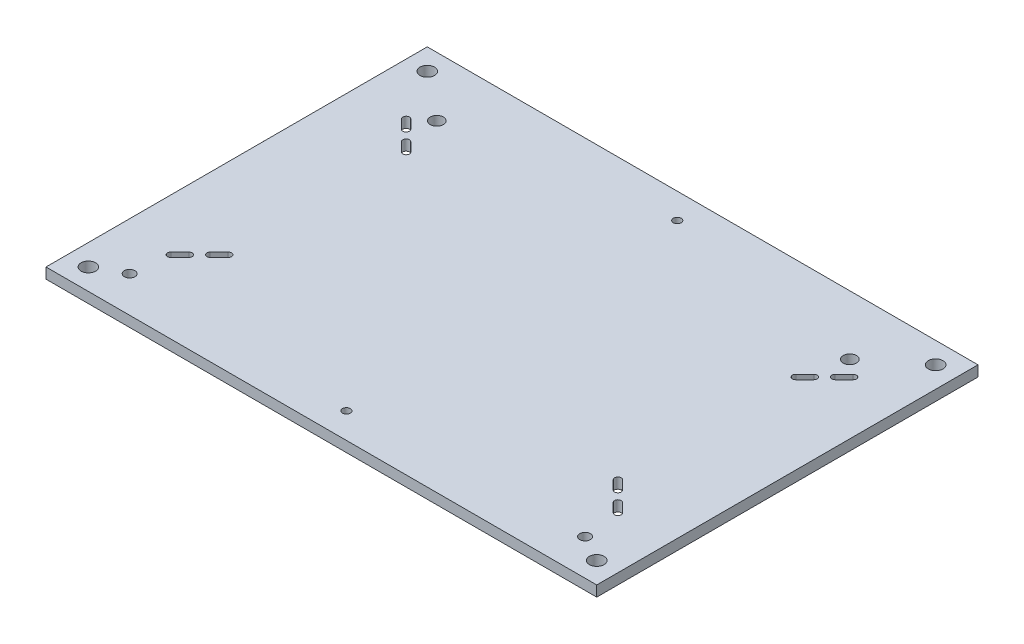
SolidWorks part; units mm, degrees
ref_plane "Front Plane" through (0, 0, 0) normal (0, 0, 1) x (1, 0, 0)
ref_plane "Top Plane" through (0, 0, 0) normal (0, 1, 0) x (1, 0, 0)
ref_plane "Right Plane" through (0, 0, 0) normal (1, 0, 0) x (0, 0, -1)
sketch "Sketch1" plane through (0, 0, 0) normal (0, 1, 0) x (1, 0, 0)
  line L1 (0, 0) -> (330.2, 0)
  line L2 (0, 0) -> (0, -228.6)
  line L3 (0, -228.6) -> (330.2, -228.6)
  line L4 (330.2, 0) -> (330.2, -228.6)
  dimension "D1" = 330.2
  dimension "D2" = 228.6
extrude "base plate" add sketch "Sketch1" against normal blind 6.35
sketch "center lines" plane through (0, 0, 0) normal (0, 1, 0) x (1, 0, 0)
  line L0 (165.1, 0) -> (165.1, -228.6) construction
  line L1 (330.2, 0) -> (0, 0) construction
  line L2 (0, -228.6) -> (330.2, -228.6) construction
  line L3 (0, -114.3) -> (330.2, -114.3) construction
  line L4 (0, 0) -> (0, -228.6) construction
  line L5 (330.2, -228.6) -> (330.2, 0) construction
sketch "Sketch3" plane through (0, 0, 0) normal (0, 1, 0) x (1, 0, 0)
  line L0 (21.0672, -185.8525) -> (30.0475, -194.8328)
  line L1 (30.0475, -194.8328) -> (60.5804, -164.2999)
  line L2 (60.5804, -164.2999) -> (51.6001, -155.3196)
  line L3 (51.6001, -155.3196) -> (21.0672, -185.8525)
  line L4 (31.0806, -184.8194) -> (36.4687, -179.4313) construction
  line L5 (29.6664, -183.4052) -> (35.0545, -178.0171)
  line L6 (32.4948, -186.2336) -> (37.8829, -180.8455)
  line L7 (0, -228.6) -> (330.2, -228.6) construction
  line L8 (48.2774, -167.6226) -> (42.8893, -173.0107) construction
  line L9 (49.6916, -169.0368) -> (44.3035, -174.425)
  line L10 (165.1, 0) -> (165.1, -228.6) construction
  line L11 (0, -114.3) -> (330.2, -114.3) construction
  line L12 (60.5804, -64.3001) -> (51.6001, -73.2804)
  line L13 (30.0475, -33.7672) -> (60.5804, -64.3001)
  line L14 (21.0672, -42.7475) -> (30.0475, -33.7672)
  line L15 (51.6001, -73.2804) -> (21.0672, -42.7475)
  line L16 (300.1525, -33.7672) -> (269.6196, -64.3001)
  line L17 (309.1328, -42.7475) -> (300.1525, -33.7672)
  line L18 (278.5999, -73.2804) -> (309.1328, -42.7475)
  line L19 (269.6196, -64.3001) -> (278.5999, -73.2804)
  line L20 (269.6196, -164.2999) -> (278.5999, -155.3196)
  line L21 (300.1525, -194.8328) -> (269.6196, -164.2999)
  line L22 (309.1328, -185.8525) -> (300.1525, -194.8328)
  line L23 (278.5999, -155.3196) -> (309.1328, -185.8525)
  line L24 (46.8632, -166.2084) -> (41.475, -171.5965)
  line L25 (31.0806, -43.7806) -> (36.4687, -49.1687) construction
  line L26 (29.6664, -45.1948) -> (35.0545, -50.5829)
  line L27 (32.4948, -42.3664) -> (37.8829, -47.7545)
  line L28 (48.2774, -60.9774) -> (42.8893, -55.5893) construction
  line L29 (49.6916, -59.5632) -> (44.3035, -54.175)
  line L30 (46.8632, -62.3916) -> (41.475, -57.0035)
  line L31 (299.1194, -43.7806) -> (293.7313, -49.1687) construction
  line L32 (300.5336, -45.1948) -> (295.1455, -50.5829)
  line L33 (297.7052, -42.3664) -> (292.3171, -47.7545)
  line L34 (281.9226, -60.9774) -> (287.3107, -55.5893) construction
  line L35 (280.5084, -59.5632) -> (285.8965, -54.175)
  line L36 (283.3368, -62.3916) -> (288.725, -57.0035)
  line L37 (281.9226, -167.6226) -> (287.3107, -173.0107) construction
  line L38 (280.5084, -169.0368) -> (285.8965, -174.425)
  line L39 (283.3368, -166.2084) -> (288.725, -171.5965)
  line L40 (299.1194, -184.8194) -> (293.7313, -179.4313) construction
  line L41 (300.5336, -183.4052) -> (295.1455, -178.0171)
  line L42 (297.7052, -186.2336) -> (292.3171, -180.8455)
  line L43 (51.6001, -164.2999) -> (51.6001, -155.3196)
  line L44 (60.5804, -164.2999) -> (51.6001, -164.2999)
  line L45 (51.6001, -64.3001) -> (51.6001, -73.2804)
  line L46 (60.5804, -64.3001) -> (51.6001, -64.3001)
  line L47 (278.5999, -64.3001) -> (278.5999, -73.2804)
  line L48 (269.6196, -64.3001) -> (278.5999, -64.3001)
  line L49 (278.5999, -164.2999) -> (278.5999, -155.3196)
  line L50 (269.6196, -164.2999) -> (278.5999, -164.2999)
  arc A0 (29.6664, -183.4052) -> (32.4948, -186.2336) centre (31.0806, -184.8194) ccw
  arc A1 (37.8829, -180.8455) -> (35.0545, -178.0171) centre (36.4687, -179.4313) ccw
  arc A2 (49.6916, -169.0368) -> (46.8632, -166.2084) centre (48.2774, -167.6226) ccw
  arc A3 (41.475, -171.5965) -> (44.3035, -174.425) centre (42.8893, -173.0107) ccw
  arc A4 (29.6664, -45.1948) -> (32.4948, -42.3664) centre (31.0806, -43.7806) cw
  arc A5 (37.8829, -47.7545) -> (35.0545, -50.5829) centre (36.4687, -49.1687) cw
  arc A6 (49.6916, -59.5632) -> (46.8632, -62.3916) centre (48.2774, -60.9774) cw
  arc A7 (41.475, -57.0035) -> (44.3035, -54.175) centre (42.8893, -55.5893) cw
  arc A8 (300.5336, -45.1948) -> (297.7052, -42.3664) centre (299.1194, -43.7806) ccw
  arc A9 (292.3171, -47.7545) -> (295.1455, -50.5829) centre (293.7313, -49.1687) ccw
  arc A10 (280.5084, -59.5632) -> (283.3368, -62.3916) centre (281.9226, -60.9774) ccw
  arc A11 (288.725, -57.0035) -> (285.8965, -54.175) centre (287.3107, -55.5893) ccw
  arc A12 (280.5084, -169.0368) -> (283.3368, -166.2084) centre (281.9226, -167.6226) cw
  arc A13 (288.725, -171.5965) -> (285.8965, -174.425) centre (287.3107, -173.0107) cw
  arc A14 (300.5336, -183.4052) -> (297.7052, -186.2336) centre (299.1194, -184.8194) cw
  arc A15 (292.3171, -180.8455) -> (295.1455, -178.0171) centre (293.7313, -179.4313) cw
  point P29 (33.7746, -182.1254)
  point P36 (45.5833, -170.3167)
  point P44 (33.7746, -46.4746)
  point P51 (45.5833, -58.2833)
  point P58 (296.4254, -46.4746)
  point P65 (284.6167, -58.2833)
  point P72 (284.6167, -170.3167)
  point P79 (296.4254, -182.1254)
  point P84 (37.8829, -178.0171)
  point P85 (41.475, -174.425)
  dimension "D6" = 2
  dimension "D10" = 5.08
  dimension "D9" = 4.699
  dimension "D1" = 43.18
  dimension "D2" = 12.7
  dimension "D3" = 45
  dimension "D4" = 99.9998
  dimension "D5" = 226.9998
  dimension "D7" = 7.62
  dimension "D8" = 6.35
extrude "slots" cut sketch "Sketch3" against normal through all contours A5 L27 A4 L26 | L33 A9 L32 A8 | L36 A11 L35 A10 | A13 L39 A12 L38 | A15 L42 A14 L41 | L6 A1 L5 A0 | L24 A3 L9 A2 | L30 A7 L29 A6 region at (33.7746, 0, 46.4746) region at (296.4254, 0, 46.4746) region at (284.6167, 0, 58.2833) region at (284.6167, 0, 170.3167) region at (296.4254, 0, 182.1254)
sketch "location of ESD" [suppressed] plane through (0, 0, 0) normal (0, 1, 0) x (1, 0, 0)
  line L0 (330.2, -228.6) -> (330.2, 0) construction
  line L1 (330.2, 0) -> (0, 0) construction
  point P0 (304.8, -114.3)
  point P3 (330.2, -114.3)
  dimension "D1" = 25.4
  dimension "D2" = 114.3
hole_wizard "Feet connection hole" positions "Sketch6" profile "Sketch7" hole size "1/4-20" standard "PEM® Inch" end condition through all
sketch "Sketch6" plane through (0, 0, 0) normal (0, 1, 0) x (1, 0, 0)
  line L0 (0, -228.6) -> (330.2, -228.6) construction
  line L1 (0, 0) -> (0, -228.6) construction
  line L2 (330.2, -228.6) -> (330.2, 0) construction
  line L3 (330.2, 0) -> (0, 0) construction
  point P3 (12.7, -215.9)
  point P19 (317.5, -12.7)
  point P31 (317.5, -215.9)
  point P33 (12.7, -12.7)
  dimension "D1" = 12.7
  dimension "D2" = 12.7
  dimension "D3" = 12.7
  dimension "D4" = 12.7
sketch "Sketch7" plane through (12.7, 0, 215.9) normal (1, 0, 0) x (0, 0, 1)
  line L0 (0, 0) -> (0, 6.35)
  line L1 (0, 6.35) -> (4.3688, 6.35)
  line L2 (4.3688, 6.35) -> (4.3688, 0)
  line L5 (4.3688, 0) -> (0, 0)
  line L11 (0, -6.35) -> (0, 107.95) construction
  dimension "Thru Hole Dia." = 8.7376
  dimension "Thru Hole Depth" = 6.35
sketch "Vacuum Chamber base hole locations" plane through (0, 0, 0) normal (0, 1, 0) x (1, 0, 0)
  line L2 (330.2, -228.6) -> (330.2, 0) construction
  line L4 (330.2, 0) -> (0, 0) construction
  point P0 (41.275, -35.56)
  point P1 (288.925, -35.56)
  point P2 (301.625, -207.01)
  point P3 (28.575, -207.01)
  dimension "D1" = 247.65
  dimension "D2" = 12.7
  dimension "D3" = 12.7
  dimension "D4" = 171.45
  dimension "D5" = 28.575
  dimension "D6" = 35.56
  dimension "D7" = 0
  dimension "D8" = 171.45
hole_wizard "1/4 (0.25) Diameter Hole1" positions "Sketch9" profile "Sketch10" hole size "1/4" standard "ANSI Inch" end condition through all
sketch "Sketch9" plane through (0, 0, 0) normal (0, 1, 0) x (1, 0, 0)
  point P0 (28.575, -207.01)
  point P3 (301.625, -207.01)
sketch "Sketch10" plane through (28.575, 0, 207.01) normal (1, 0, 0) x (0, 0, 1)
  line L0 (0, 0) -> (0, 6.35)
  line L1 (0, 6.35) -> (3.175, 6.35)
  line L2 (3.175, 6.35) -> (3.175, 0)
  line L5 (3.175, 0) -> (0, 0)
  line L11 (0, -6.35) -> (0, 107.95) construction
  dimension "Thru Hole Dia." = 6.35
  dimension "Thru Hole Depth" = 6.35
hole_wizard "5/16 (0.3125) Diameter Hole1" positions "Sketch11" profile "Sketch12" hole size "5/16" standard "ANSI Inch" end condition through all
sketch "Sketch11" plane through (0, 0, 0) normal (0, 1, 0) x (1, 0, 0)
  point P0 (41.275, -35.56)
  point P3 (288.925, -35.56)
sketch "Sketch12" plane through (41.275, 0, 35.56) normal (1, 0, 0) x (0, 0, 1)
  line L0 (0, 0) -> (0, 6.35)
  line L1 (0, 6.35) -> (3.9687, 6.35)
  line L2 (3.9687, 6.35) -> (3.9687, 0)
  line L5 (3.9687, 0) -> (0, 0)
  line L11 (0, -6.35) -> (0, 107.95) construction
  dimension "Thru Hole Dia." = 7.9375
  dimension "Thru Hole Depth" = 6.35
sketch "Sketch14" plane through (0, 0, 0) normal (0, 1, 0) x (1, 0, 0)
  line L2 (0, 0) -> (0, -228.6) construction
  line L3 (330.2, 0) -> (0, 0) construction
  line L4 (0, -228.6) -> (330.2, -228.6) construction
  point P0 (165.1, -15.24)
  point P1 (165.1, -213.36)
  dimension "D1" = 165.1
  dimension "D2" = 15.24
  dimension "D3" = 165.1
  dimension "D4" = 15.24
hole_wizard "ESD Connection hole" positions "Sketch15" profile "Sketch16" hole size "#6-32" standard "PEM® Inch" end condition through all
sketch "Sketch15" plane through (0, 0, 0) normal (0, 1, 0) x (1, 0, 0)
  point P0 (165.1, -15.24)
  point P3 (164.7687, -213.267)
sketch "Sketch16" plane through (165.1, 0, 15.24) normal (1, 0, 0) x (0, 0, 1)
  line L0 (0, 0) -> (0, 6.35)
  line L1 (0, 6.35) -> (2.3812, 6.35)
  line L2 (2.3812, 6.35) -> (2.3812, 0)
  line L5 (2.3812, 0) -> (0, 0)
  line L11 (0, -6.35) -> (0, 107.95) construction
  dimension "Thru Hole Dia." = 4.7625
  dimension "Thru Hole Depth" = 6.35
